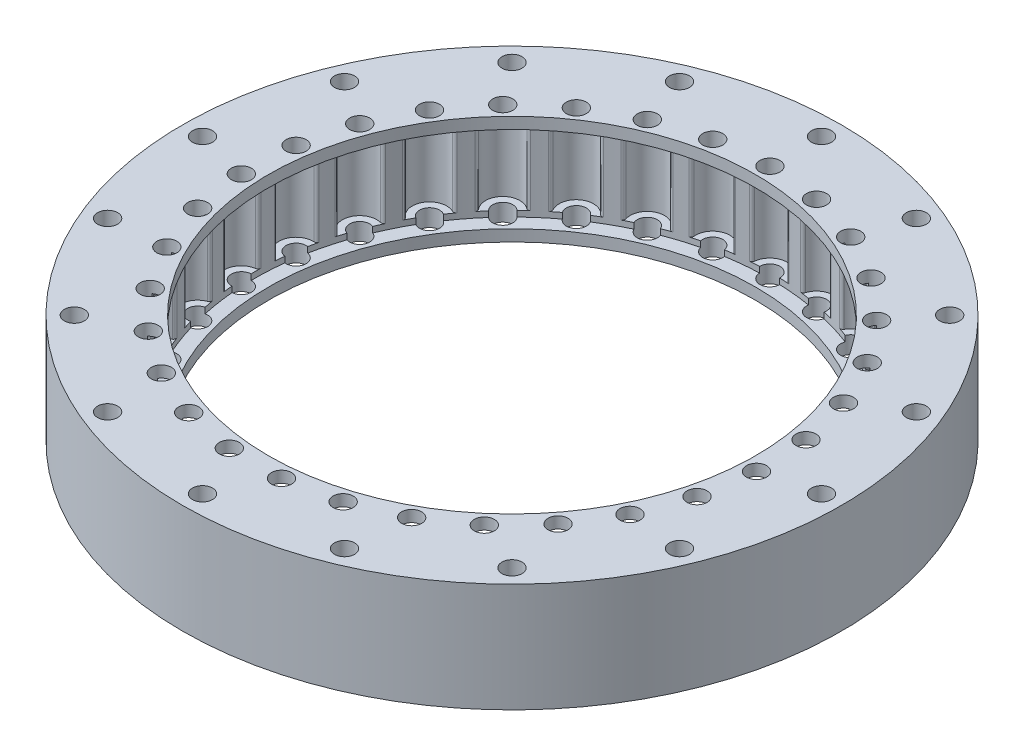
SolidWorks part; units mm, degrees
other "Markup1"
sketch "Sketch12" plane through (-57.5, 16, 57.5) normal (-0.5757, 0.7687, 0.2786) x (0.7628, 0.3823, 0.5216)
other "Markup2"
sketch "Sketch13" plane through (-57.5, 16, 57.5) normal (-0.5757, 0.7687, 0.2786) x (0.7628, 0.3823, 0.5216)
ref_plane "Front Plane" through (0, 0, 0) normal (0, 0, 1) x (1, 0, 0)
ref_plane "Top Plane" through (0, 0, 0) normal (0, 1, 0) x (1, 0, 0)
ref_plane "Right Plane" through (0, 0, 0) normal (1, 0, 0) x (0, 0, -1)
sketch "Sketch1" plane through (0, 0, 0) normal (0, 1, 0) x (1, 0, 0)
  line L0 (15.8389, 51.6249) -> (0, 0) construction
  line L1 (0, 0) -> (-4.5526, -44.7691) construction
  circle A0 centre (0, 0) radius 45
  circle A12 centre (0, 0) radius 57.5
  circle A13 centre (0, 0) radius 54 construction
  point P27 (0, 0)
  point P54 (0, 0)
  dimension "D1" = 90
  dimension "D4" = 115
  dimension "D5" = 108
  dimension "D8" = 11.25
extrude "Boss-Extrude1" add sketch "Sketch1" along normal blind 13 contours A12 region at (-55.8737, 0, 0)
sketch "Sketch2" plane through (0, 0, 0) normal (0, -1, 0) x (1, 0, 0)
  circle A0 centre (0, 0) radius 57.5
  circle A1 centre (0, 0) radius 45
extrude "Boss-Extrude2" add sketch "Sketch2" along normal blind 1
sketch "Sketch3" plane through (0, -1, 0) normal (0, -1, 0) x (1, 0, 0)
  circle A0 centre (0, 0) radius 57.5
  circle A1 centre (0, 0) radius 42.5
  dimension "D1" = 85
extrude "Boss-Extrude3" add sketch "Sketch3" along normal blind 2
sketch "Sketch5" plane through (0, 13, 0) normal (0, 1, 0) x (1, 0, 0)
  circle A0 centre (0, 45) radius 3
  circle A1 centre (0, 0) radius 45 construction
  circle A2 centre (0, 0) radius 45 construction
  dimension "D1" = 6
extrude "Cut-Extrude2" cut sketch "Sketch5" against normal blind 13
fillet "Fillet4" radius 0.5 2 edges at (2.9983, 6.5, -44.9) (-2.9983, 6.5, -44.9)
sketch "Sketch10" plane through (0, 13, 0) normal (0, 1, 0) x (1, 0, 0)
  circle A0 centre (0, 0) radius 45
  circle A1 centre (0, 0) radius 57.5
extrude "Boss-Extrude4" add sketch "Sketch10" along normal blind 1
sketch "Sketch11" plane through (0, 14, 0) normal (0, 1, 0) x (1, 0, 0)
  circle A0 centre (0, 0) radius 42.5
  circle A1 centre (0, 0) radius 57.5
extrude "Boss-Extrude5" add sketch "Sketch11" along normal blind 2
sketch "Sketch7" plane through (0, 16, 0) normal (0, 1, 0) x (1, 0, 0)
  circle A0 centre (0, 45) radius 1.75
  arc A1 (3.4425, 44.8681) -> (-3.4425, 44.8681) centre (0, 0) ccw construction
  dimension "D1" = 3.5
extrude "Cut-Extrude3" cut sketch "Sketch7" against normal blind 23
pattern_circular "CirPattern3" count 31 over 360 about axis through (0, -3, 0) along (0, 1, 0) of "Cut-Extrude2", "Fillet4", "Cut-Extrude3"
sketch "Sketch4" plane through (0, 16, 0) normal (0, 1, 0) x (1, 0, 0)
  circle A0 centre (0, 0) radius 54 construction
  circle A1 centre (0, 54) radius 1.75
  circle A2 centre (20.6649, 49.8895) radius 1.75
  circle A3 centre (38.1838, 38.1838) radius 1.75
  circle A4 centre (49.8895, 20.6649) radius 1.75
  circle A5 centre (54, 0) radius 1.75
  circle A6 centre (49.8895, -20.6649) radius 1.75
  circle A7 centre (38.1838, -38.1838) radius 1.75
  circle A8 centre (20.6649, -49.8895) radius 1.75
  circle A9 centre (0, -54) radius 1.75
  circle A10 centre (-20.6649, -49.8895) radius 1.75
  circle A11 centre (-38.1838, -38.1838) radius 1.75
  circle A12 centre (-49.8895, -20.6649) radius 1.75
  circle A13 centre (-54, 0) radius 1.75
  circle A14 centre (-49.8895, 20.6649) radius 1.75
  circle A15 centre (-38.1838, 38.1838) radius 1.75
  circle A16 centre (-20.6649, 49.8895) radius 1.75
  circle A17 centre (0, 0) radius 45 construction
  point P38 (0, 0)
  point P102 (0, 0)
  dimension "D1" = 108
  dimension "D2" = 3.5
extrude "Cut-Extrude1" cut sketch "Sketch4" against normal blind 51
